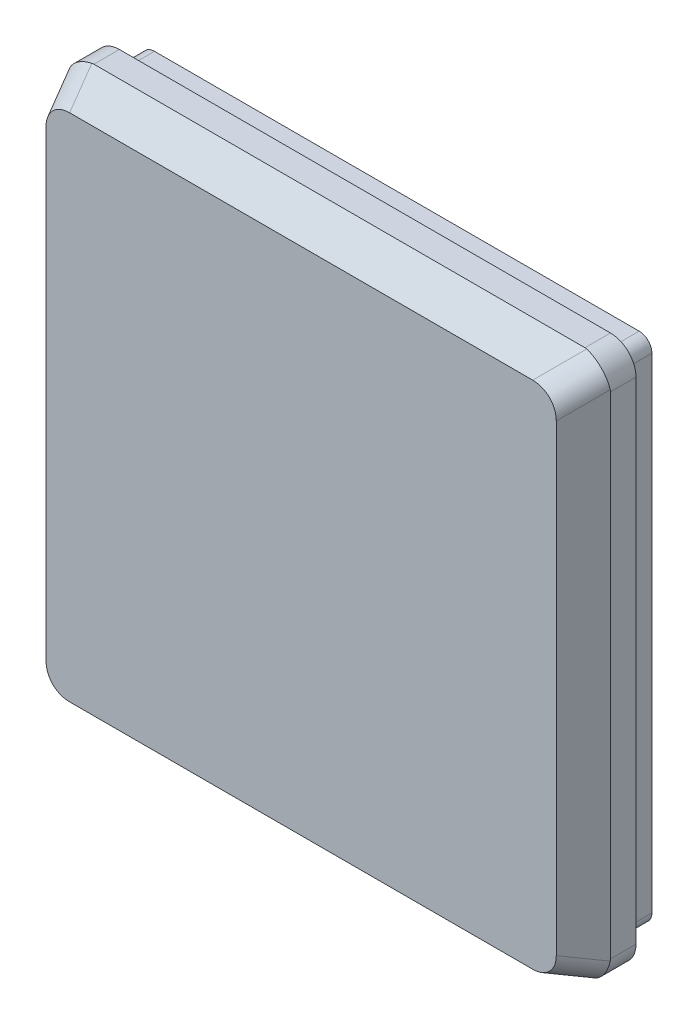
SolidWorks part; units mm, degrees
ref_plane "Ebene vorne" through (0, 0, 0) normal (0, 0, 1) x (1, 0, 0)
ref_plane "Ebene oben" through (0, 0, 0) normal (0, 1, 0) x (1, 0, 0)
ref_plane "Ebene rechts" through (0, 0, 0) normal (1, 0, 0) x (0, 0, -1)
sketch "Skizze1" plane through (0, 0, 0) normal (0, 0, 1) x (1, 0, 0)
  line L1 (-80, -80) -> (80, -80)
  line L2 (-80, -80) -> (-80, 80)
  line L3 (-80, 80) -> (80, 80)
  line L4 (80, -80) -> (80, 80)
  line L5 (-80, -80) -> (80, 80) construction
  line L6 (-80, 80) -> (80, -80) construction
  point P0 (0, 0)
  dimension "D1" = 160
extrude "Aufsatz-Linear austragen1" add sketch "Skizze1" along normal blind 10
sketch "Skizze2" plane through (0, 0, 10) normal (0, 0, 1) x (1, 0, 0)
  line L0 (80, 80) -> (-80, 80) construction
  line L1 (-85, -85) -> (85, -85)
  line L2 (-85, -85) -> (-85, 85)
  line L3 (-85, 85) -> (85, 85)
  line L4 (85, -85) -> (85, 85)
  line L5 (-85, -85) -> (85, 85) construction
  line L6 (-85, 85) -> (85, -85) construction
  point P0 (0, 0)
  dimension "D1" = 5
extrude "Aufsatz-Linear austragen2" add sketch "Skizze2" along normal blind 20
chamfer "Fase1" distance 12 distance2 5 4 edges at (85, 0, 30) (0, -85, 30) (-85, 0, 30) (0, 85, 30) first distance on face at (85, 0, 20) first distance on face at (0, -85, 20) first distance on face at (-85, 0, 20) first distance on face at (0, 85, 20)
fillet "Verrundung1" radius 8 8 edges at (-82.5, 82.5, 24) (-82.5, -82.5, 24) (82.5, -82.5, 24) (85, -85, 14) (82.5, 82.5, 24) (-85, -85, 14) (-85, 85, 14) (85, 85, 14)
fillet "Verrundung2" radius 4 4 edges at (80, 80, 5) (80, -80, 5) (-80, -80, 5) (-80, 80, 5)
